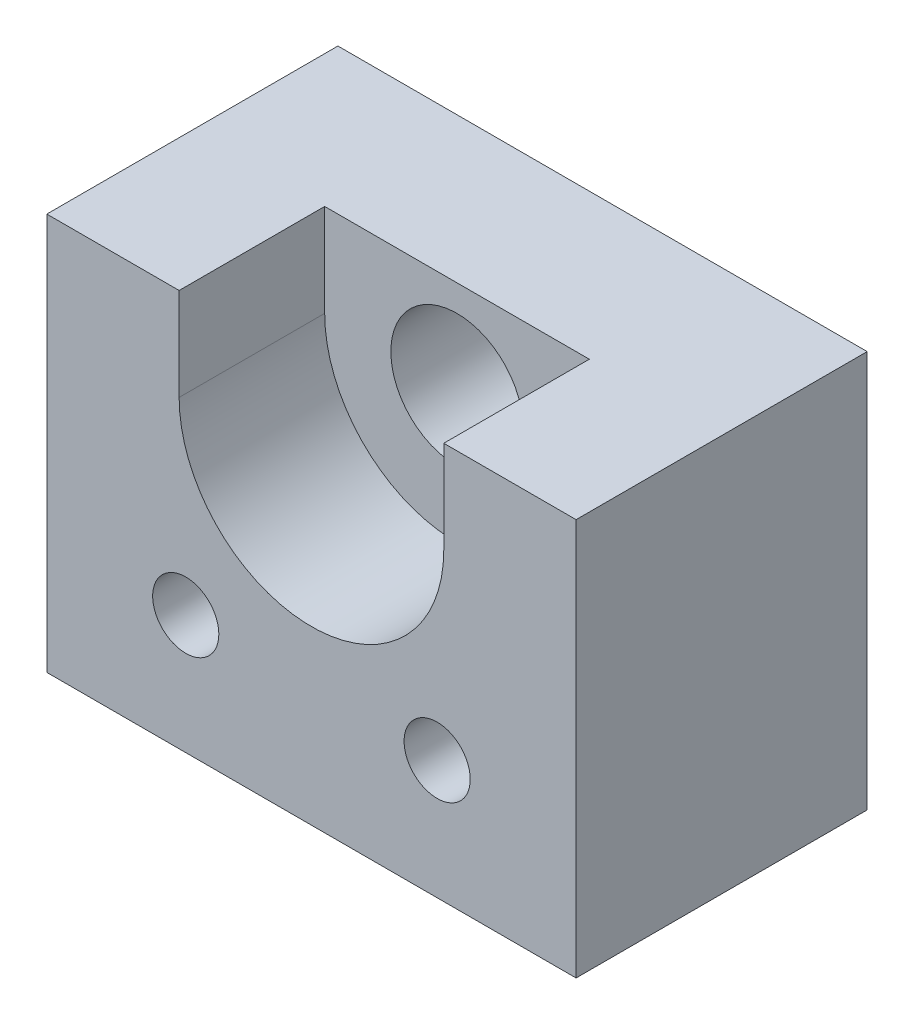
SolidWorks part; units mm, degrees
ref_plane "Front Plane" through (0, 0, 0) normal (0, 0, 1) x (1, 0, 0)
ref_plane "Top Plane" through (0, 0, 0) normal (0, 1, 0) x (1, 0, 0)
ref_plane "Right Plane" through (0, 0, 0) normal (1, 0, 0) x (0, 0, -1)
sketch "Sketch1" plane through (0, 0, 0) normal (0, 0, 1) x (1, 0, 0)
  line L0 (10, 0) -> (10, 11.5) construction
  line L1 (0, 0) -> (20, 0)
  line L2 (0, 0) -> (0, 15)
  line L3 (0, 15) -> (20, 15)
  line L4 (20, 0) -> (20, 15)
  circle A0 centre (10, 11.5) radius 2.5
  circle A1 centre (5.25, 4.5) radius 1.25
  circle A2 centre (14.75, 4.5) radius 1.25
  dimension "D4" = 2.5
  dimension "D5" = 2.5
  dimension "D6" = 9.5
  dimension "D8" = 5
  dimension "D1" = 20
  dimension "D2" = 15
  dimension "D3" = 4.5
  dimension "D7" = 4.75
  dimension "D9" = 3.5
extrude "Boss-Extrude1" add sketch "Sketch1" along normal blind 11
sketch "Sketch2" plane through (0, 0, 11) normal (0, 0, 1) x (1, 0, 0)
  line L0 (15, 11.5) -> (15, 15)
  line L1 (20, 15) -> (0, 15) construction
  line L2 (15, 15) -> (5, 15)
  line L3 (5, 15) -> (5, 11.5)
  arc A0 (5, 11.5) -> (15, 11.5) centre (10, 11.5) ccw
  circle A1 centre (10, 11.5) radius 2.5 construction
  dimension "D1" = 10
extrude "Cut-Extrude1" cut sketch "Sketch2" against normal blind 5.5
sketch "Sketch3" plane through (0, 0, 0) normal (0, 0, -1) x (-1, 0, 0)
  line L0 (0, 0) -> (-20, 0) construction
  line L1 (-12.4, 0) -> (-7.6, 0)
  line L2 (-12.4, 0) -> (-12.4, 6)
  line L3 (-12.4, 6) -> (-7.6, 6)
  line L4 (-7.6, 0) -> (-7.6, 6)
  circle A0 centre (-10, 11.5) radius 2.5 construction
  dimension "D1" = 5.5
  dimension "D2" = 4.8
  dimension "D3" = 2.4
extrude "Boss-Extrude2" add sketch "Sketch3" along normal blind 5
chamfer "Chamfer1" distance 5 angle 45 1 edges at (10, 6, -5)
